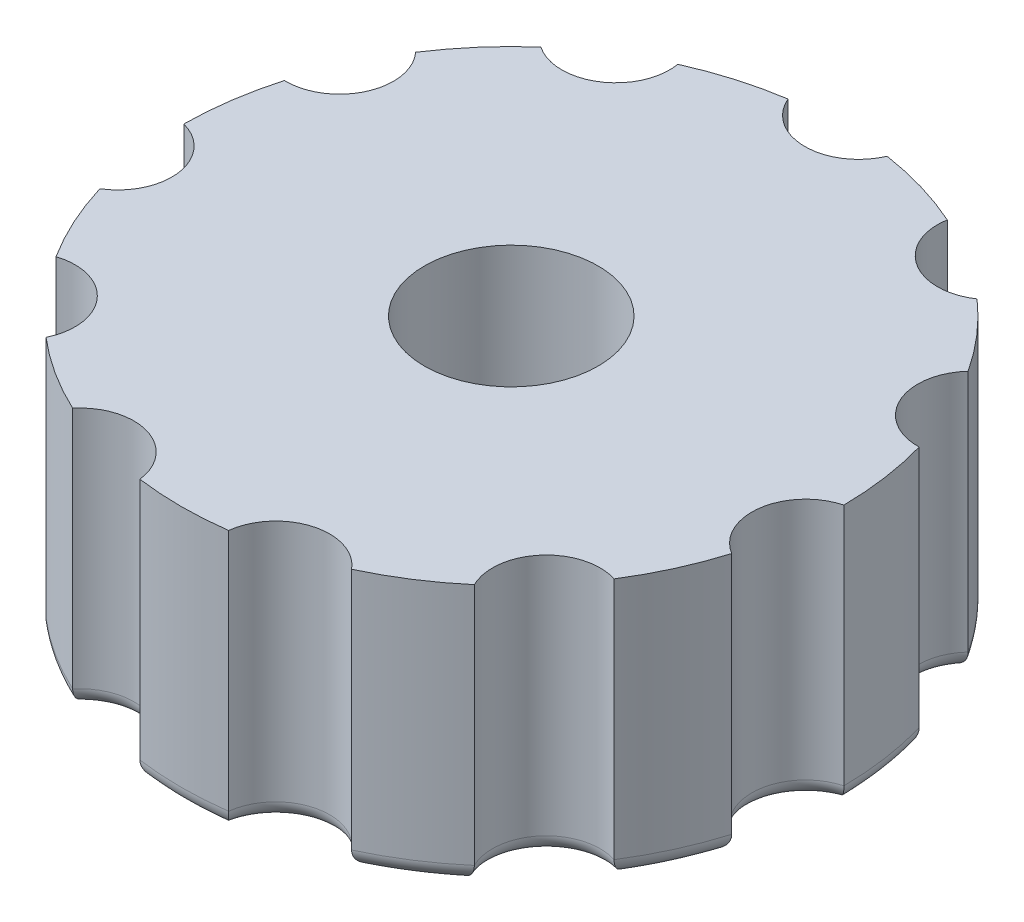
SolidWorks part; units mm, degrees
ref_plane "Front Plane" through (0, 0, 0) normal (0, 0, 1) x (1, 0, 0)
ref_plane "Top Plane" through (0, 0, 0) normal (0, 1, 0) x (1, 0, 0)
ref_plane "Right Plane" through (0, 0, 0) normal (1, 0, 0) x (0, 0, -1)
sketch "Sketch1" plane through (0, 0, 0) normal (0, 1, 0) x (1, 0, 0)
  line L0 (0, 10) -> (0, 9.5) construction
  circle A0 centre (0, 0) radius 9.5
  circle A1 centre (0, 0) radius 2.5
  circle A2 centre (0, 10) radius 1.55
  dimension "D1" = 19
  dimension "D2" = 5
  dimension "D3" = 3.1
  dimension "D4" = 0.5
extrude "Boss-Extrude1" add sketch "Sketch1" along normal blind 7.5 contours A2 A0 A1 | A0 A2 region at (-6.0182, 0, 7.0009) region at (0, 0, -9.0447)
extrude "Boss-Extrude2" add sketch "Sketch1<3>" along normal blind 2 contours A1
sketch "Sketch1<3>" plane through (0, 0, 0) normal (0, 1, 0) x (1, 0, 0) same geometry as "Sketch1"
ref_axis "Axis1" through (0, 0, 0) along (0, 1, 0)
extrude "Cut-Extrude1" cut sketch "Sketch1<4>" along normal through all contours A2
sketch "Sketch1<4>" plane through (0, 0, 0) normal (0, 1, 0) x (1, 0, 0) same geometry as "Sketch1"
pattern_circular "CirPattern1" count 11 over 360 about axis through (0, 0, 0) along (0, 1, 0) of "Cut-Extrude1"
fillet "Fillet1" radius 0.5 22 edges at (-9.4033, 0, -1.352) (-8.364, 0, 1.2026) (-8.6415, 0, 3.9464) (-6.3861, 0, 5.5336) (-5.1361, 0, 7.9919) (-2.3806, 0, 8.1077) (0, 0, 9.5) (2.3806, 0, 8.1077) (5.1361, 0, 7.9919) (6.3861, 0, 5.5336) (8.6415, 0, 3.9464) (0, 0, -8.45) (-2.6765, 0, -9.1152) (-4.5684, 0, -7.1086) (-7.1796, 0, -6.2212) (-7.6864, 0, -3.5103) (8.364, 0, 1.2026) (9.4033, 0, -1.352) (7.6864, 0, -3.5103) (7.1796, 0, -6.2212) (4.5684, 0, -7.1086) (2.6765, 0, -9.1152)
